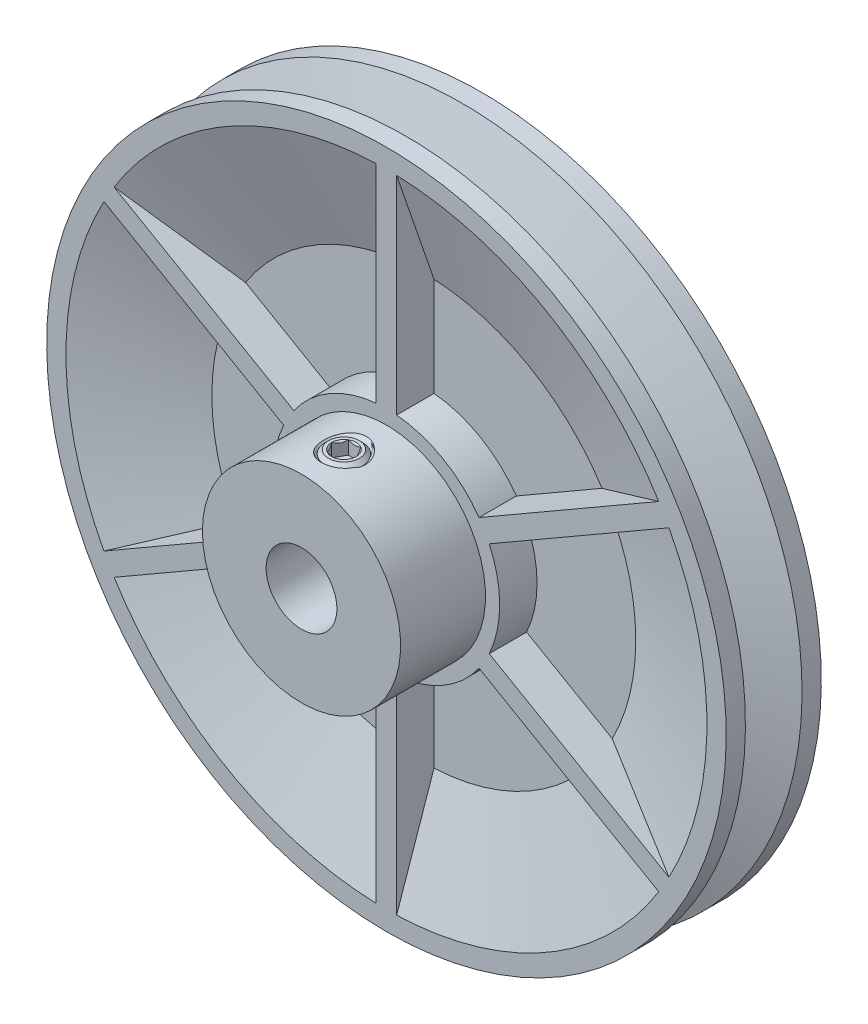
SolidWorks part; units mm, degrees
material "Nylon 101"
ref_plane "Front Plane" through (0, 0, 0) normal (0, 0, 1) x (1, 0, 0)
ref_plane "Top Plane" through (0, 0, 0) normal (0, 1, 0) x (1, 0, 0)
ref_plane "Right Plane" through (0, 0, 0) normal (1, 0, 0) x (0, 0, -1)
sketch "Sketch1" plane through (0, 0, 0) normal (1, 0, 0) x (0, 0, -1)
  line L0 (-14.859, 0) -> (7.366, 0) construction
  line L1 (-3.175, 38.1) -> (3.175, 38.1) construction
  line L2 (3.175, 38.1) -> (5.334, 38.1)
  line L5 (-5.334, 38.1) -> (7.366, 38.1) construction
  line L7 (-5.334, 7.9375) -> (-5.334, 38.1) construction
  line L9 (5.334, 7.9375) -> (-5.334, 7.9375)
  line L10 (-5.334, 35.941) -> (-1.143, 23.7695)
  line L12 (7.366, 38.1) -> (7.366, 0) construction
  line L13 (-3.175, 38.1) -> (-0.9885, 31.75)
  line L14 (-0.9885, 31.75) -> (0.9885, 31.75)
  line L15 (0.9885, 31.75) -> (3.175, 38.1)
  line L16 (7.366, 3.9687) -> (-14.859, 3.9687) construction
  line L17 (0, 38.1) -> (0, 0) construction
  line L18 (-3.175, 38.1) -> (-5.334, 38.1)
  line L20 (-14.859, 0) -> (-14.859, 3.9687) construction
  line L22 (5.334, 36.83) -> (-5.334, 36.83) construction
  line L23 (5.334, 12.7) -> (5.334, 38.1) construction
  line L24 (5.334, 35.941) -> (1.143, 23.7695)
  line L25 (-1.143, 23.7695) -> (-1.143, 12.7)
  line L26 (1.143, 23.7695) -> (1.143, 12.7)
  line L27 (-1.143, 23.7695) -> (1.143, 23.7695) construction
  line L28 (5.334, 7.9375) -> (5.334, 12.7)
  line L29 (5.334, 12.7) -> (1.143, 12.7)
  line L30 (-5.334, 12.7) -> (-5.334, 7.9375)
  line L31 (-1.143, 12.7) -> (-5.334, 12.7)
  line L32 (-5.334, 35.941) -> (-5.334, 38.1)
  line L33 (5.334, 38.1) -> (5.334, 35.941)
  point P16 (0, 31.75)
  point P34 (0, 23.7695)
  dimension "D1" = 9.525
  dimension "A" = 38
  dimension "D2" = 15.875
  dimension "OD" = 76.2
  dimension "D3" = 10.668
  dimension "D4" = 2.286
  dimension "D5" = 25.4
  dimension "Bore" = 7.9375
  dimension "Width" = 22.225
  dimension "PD" = 73.66
  dimension "W" = 6.35
  dimension "Depth" = 6.35
revolve "Revolve1" add sketch "Sketch1" angle 360 about L0
sketch "Sketch2" plane through (0, 0, 0) normal (1, 0, 0) x (0, 0, -1)
  line L1 (-1.143, 23.7695) -> (-1.143, 12.7) construction
  line L3 (-5.334, 35.941) -> (-1.143, 23.7695) construction
  line L4 (-1.143, 23.7695) -> (-1.143, 7.9375)
  line L5 (-1.143, 7.9375) -> (-5.334, 7.9375)
  line L6 (-5.334, 35.941) -> (-1.143, 23.7695)
  line L7 (-5.334, 35.941) -> (-5.334, 7.9375)
  line L11 (5.334, 7.9375) -> (-5.334, 7.9375) construction
  line L12 (-5.334, 12.7) -> (-5.334, 7.9375) construction
  line L13 (0, 0) -> (0, 38.1) construction
  line L14 (5.334, 35.941) -> (5.334, 7.9375)
  line L15 (5.334, 35.941) -> (1.143, 23.7695)
  line L16 (1.143, 7.9375) -> (5.334, 7.9375)
  line L17 (1.143, 23.7695) -> (1.143, 7.9375)
extrude "Boss-Extrude1" add sketch "Sketch2" along normal mid plane 2.286
pattern_circular "CirPattern1" count 6 over 360 about axis through (0, 0, 14.859) along (0, 0, 1) of "Boss-Extrude1"
sketch "Sketch3" plane through (0, 0, 0) normal (1, 0, 0) x (0, 0, -1)
  line L0 (7.366, 0) -> (-14.859, 0) construction
  line L1 (7.366, 0) -> (7.366, 7.9375)
  line L2 (7.366, 7.9375) -> (-5.334, 7.9375)
  line L3 (-5.334, 7.9375) -> (-5.334, 11.1125)
  line L4 (-5.334, 11.1125) -> (-14.859, 11.1125)
  line L5 (-14.859, 11.1125) -> (-14.859, 0)
  line L6 (5.334, 7.9375) -> (-5.334, 7.9375) construction
  line L7 (-5.334, 12.7) -> (-5.334, 7.9375) construction
  line L8 (-14.859, 0) -> (7.366, 0)
  dimension "D1" = 22.225
revolve "Revolve2" add sketch "Sketch3" angle 360 about L0
sketch "Sketch4" plane through (0, 0, -7.366) normal (0, 0, -1) x (-1, 0, 0)
  circle A0 centre (0, 0) radius 3.9687
  circle A1 centre (0, 0) radius 36.83 construction
extrude "Cut-Extrude1" cut sketch "Sketch4" against normal up to vertex (22.225 mm away) up to point (0, 0, 14.859)
ref_plane "Plane1" through (0, 11.1125, 0) normal (0, 1, 0) x (-1, 0, 0)
sketch "Sketch5" plane through (0, 11.1125, 0) normal (0, 1, 0) x (-1, 0, 0)
  line L0 (0, 5.334) -> (0, 14.859) construction
  line L7 (0, 12.5095) -> (0, 11.4512) construction
  circle A0 centre (0, 10.0965) radius 2.413 construction
  circle A1 centre (0, 10.0965) radius 1.7515
  dimension "D1" = 4.826
  dimension "D2" = 1.0583
  dimension "D3" = 0.6615
extrude "Cut-Extrude2" cut sketch "Sketch5" against normal up to surface (11.1125 mm away) up to plane "Top Plane"
sketch "Sketch6" plane through (0, 11.1125, 0) normal (0, 1, 0) x (-1, 0, 0)
  circle A0 centre (0, 10.0965) radius 2.413 construction
  circle A1 centre (0, 10.0965) radius 2.413
  point P3 (0, 12.5095)
curve "Helix/Spiral1" pitch 1.0583 height 12.1708 radius 2.413 centre (0, 11.1125, 10.0965) axis (0, -1, 0) start towards (0, 0, 1)
sketch "Sketch7" plane through (0, 0, 0) normal (1, 0, 0) x (0, 0, -1)
  line L0 (-11.7075, 12.1708) -> (-11.7075, 11.1125) construction
  line L1 (-11.7075, 11.1125) -> (-12.6241, 11.6417) construction
  line L2 (-12.6241, 11.6417) -> (-11.7075, 12.1708) construction
  line L3 (-11.7075, 11.1125) -> (-12.5095, 11.1125) construction
  line L4 (-12.5095, 11.1125) -> (-12.5095, 11.5755) construction
  line L5 (-12.5095, 11.5755) -> (-12.5095, 11.7078) construction
  line L6 (-11.8221, 11.1786) -> (-11.8221, 12.1047) construction
  line L7 (-12.6241, 11.6417) -> (-12.5095, 11.6417) construction
  line L8 (-11.8221, 11.6417) -> (-11.7075, 11.6417) construction
  line L9 (-11.7648, 12.1378) -> (-11.7648, 11.1456)
  line L10 (-11.7648, 11.1456) -> (-12.5095, 11.5755)
  line L11 (-12.5095, 11.5755) -> (-12.5095, 11.7078)
  line L12 (-12.5095, 11.7078) -> (-11.7648, 12.1378)
  point P16 (-11.7648, 11.6417)
  dimension "D1" = 1.0583
  dimension "D2" = 0.1323
sweep "Cut-Sweep1" cut profiles "Sketch7" path "Helix/Spiral1" align with end faces yes
sketch "Sketch8" plane through (0, 11.1125, 0) normal (0, 1, 0) x (-1, 0, 0)
  circle A0 centre (0, 10.0965) radius 2.5276
extrude "Cut-Extrude3" cut sketch "Sketch8" against normal through all draft 45
sketch "Sketch9" plane through (0, 0, 0) normal (1, 0, 0) x (0, 0, -1)
  line L0 (-10.0965, 11.1125) -> (-10.0965, 4.7625) construction
  line L1 (-12.5095, 5.4499) -> (-12.5095, 10.4251)
  line L2 (-10.0965, 11.1125) -> (-12.5095, 11.1125) construction
  line L3 (-10.0965, 11.1125) -> (-10.0965, 4.7625)
  line L4 (-10.0965, 4.7625) -> (-12.5095, 4.7625) construction
  line L5 (-12.5095, 11.1125) -> (-12.5095, 4.7625) construction
  line L6 (-11.8221, 11.1125) -> (-12.5095, 10.4251)
  line L7 (-12.5095, 5.4499) -> (-11.8221, 4.7625)
  line L8 (-11.8221, 11.1125) -> (-10.0965, 11.1125)
  line L9 (-11.8221, 4.7625) -> (-10.0965, 4.7625)
  line L10 (-5.334, 11.1125) -> (-14.859, 11.1125) construction
  line L11 (-11.8221, 11.1125) -> (-12.5095, 11.1125) construction
  line L12 (-12.5095, 11.1125) -> (-12.5095, 10.4251) construction
  line L13 (-11.8221, 11.1786) -> (-11.8221, 12.1047) construction
  dimension "D1" = 6.35
revolve "Revolve3" add sketch "Sketch9" angle 360 about L0
sketch "Sketch10" plane through (0, 11.1125, 0) normal (0, 1, 0) x (1, 0, 0)
  line L1 (1.3748, -10.0965) -> (0.6874, -8.9059)
  line L2 (0.6874, -8.9059) -> (-0.6874, -8.9059)
  line L3 (-0.6874, -8.9059) -> (-1.3748, -10.0965)
  line L4 (-1.3748, -10.0965) -> (-0.6874, -11.2871)
  line L5 (-0.6874, -11.2871) -> (0.6874, -11.2871)
  line L6 (0.6874, -11.2871) -> (1.3748, -10.0965)
  circle A0 centre (0, -10.0965) radius 1.1906 construction
  dimension "D1" = 2.3813
extrude "Cut-Extrude4" cut sketch "Sketch10" against normal blind 1.4883
sketch "Sketch11" plane through (0, 11.1125, 0) normal (0, 1, 0) x (1, 0, 0)
  circle A0 centre (0, -10.0965) radius 1.3748
extrude "Cut-Extrude5" cut sketch "Sketch11" against normal through all draft 45
equation "\"D3@Sketch5\" = \"D2@Sketch5\" * 5 / 8"
equation "\"D4@Helix/Spiral1\" = \"D2@Sketch5\""
equation "\"D3@Helix/Spiral1\" = \"D4@Helix/Spiral1\" + ( \"D1@Sketch3\" / 2 ) "
equation "\"D1@Sketch7\" = \"D4@Helix/Spiral1\""
equation "\"D2@Sketch7\" = \"D1@Sketch7\" / 8"
